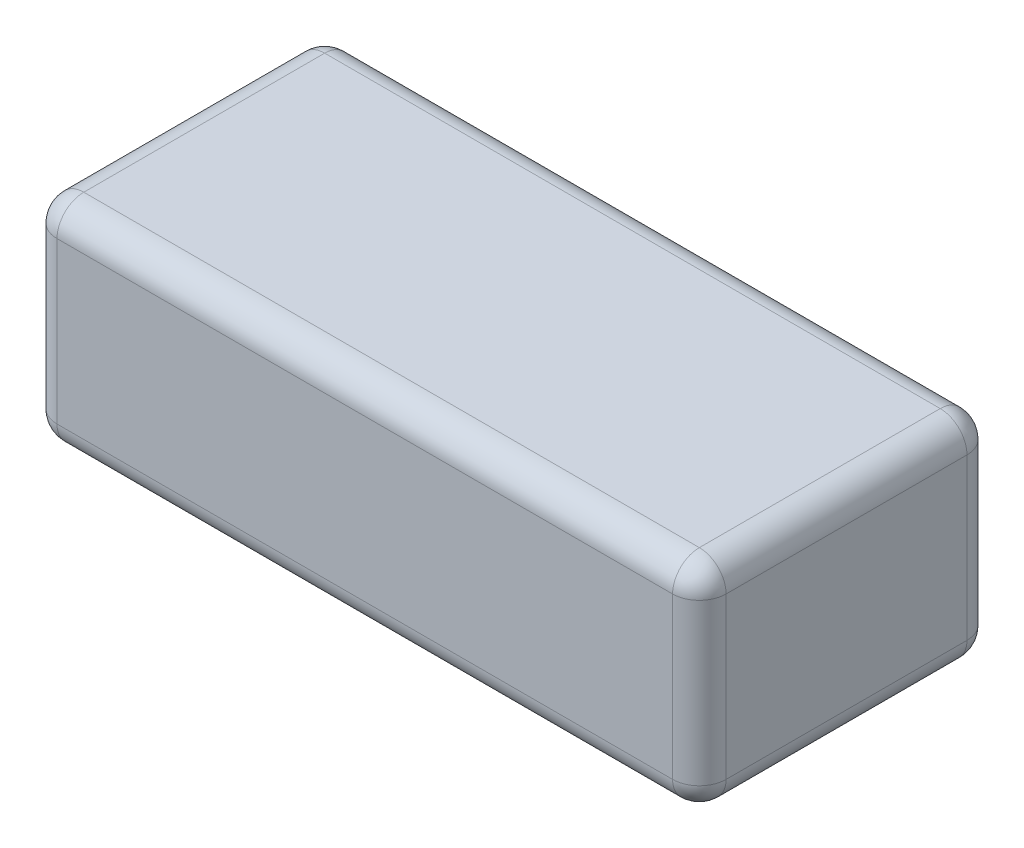
SolidWorks part; units mm, degrees
ref_plane "前视基准面" through (0, 0, 0) normal (0, 0, 1) x (1, 0, 0)
ref_plane "上视基准面" through (0, 0, 0) normal (0, 1, 0) x (1, 0, 0)
ref_plane "右视基准面" through (0, 0, 0) normal (1, 0, 0) x (0, 0, -1)
other "Configuration Table"
sketch "草图1" plane through (0, 0, 0) normal (0, 0, 1) x (1, 0, 0)
  line L1 (-25, -8) -> (25, -8)
  line L2 (-25, -8) -> (-25, 8)
  line L3 (-25, 8) -> (25, 8)
  line L4 (25, -8) -> (25, 8)
  line L5 (-25, -8) -> (25, 8) construction
  line L6 (-25, 8) -> (25, -8) construction
extrude "凸台-拉伸1" add sketch "草图1" along normal mid plane 22
fillet "圆角1" radius 2 12 edges at (25, 0, -11) (0, 8, -11) (-25, 0, -11) (0, -8, -11) (25, 0, 11) (0, 8, 11) (-25, 0, 11) (0, -8, 11) (25, -8, 0) (-25, -8, 0) (-25, 8, 0) (25, 8, 0) tangent propagation no
